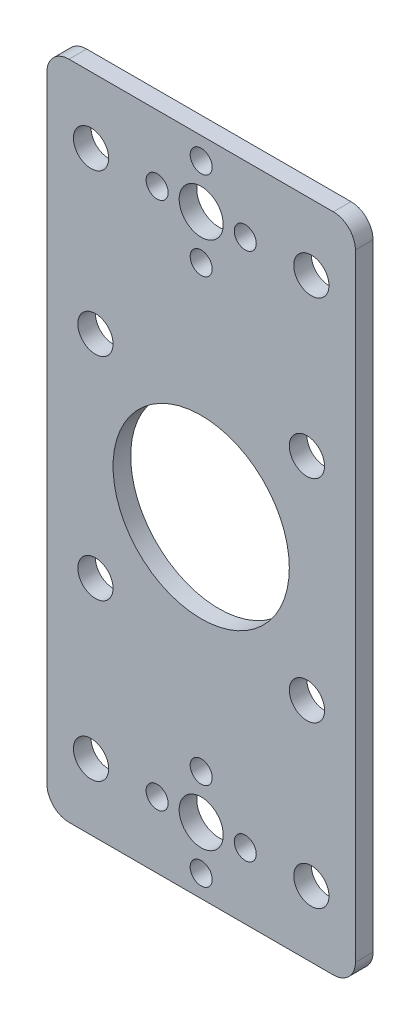
SolidWorks part; units mm, degrees
ref_plane "Front Plane" through (0, 0, 0) normal (0, 0, 1) x (1, 0, 0)
ref_plane "Top Plane" through (0, 0, 0) normal (0, 1, 0) x (1, 0, 0)
ref_plane "Right Plane" through (0, 0, 0) normal (1, 0, 0) x (0, 0, -1)
sketch "Sketch1" plane through (0, 0, 0) normal (0, 0, 1) x (1, 0, 0)
  line L0 (1.0283, 75.669) -> (1.0283, -74.331) construction
  line L1 (-59.1034, 0.669) -> (56.16, 0.669) construction
  line L2 (-50.4717, 60.669) -> (47.5283, 60.669) construction
  line L3 (36.0283, -74.331) -> (-33.9717, -74.331)
  line L4 (36.0283, -74.331) -> (36.0283, 75.669)
  line L5 (36.0283, 75.669) -> (-33.9717, 75.669)
  line L6 (-33.9717, -74.331) -> (-33.9717, 75.669)
  line L7 (36.0283, -74.331) -> (-33.9717, 75.669) construction
  line L8 (36.0283, 75.669) -> (-33.9717, -74.331) construction
  line L9 (-22.9717, -23.331) -> (25.0283, -23.331) construction
  line L10 (-22.9717, -23.331) -> (-22.9717, 24.669) construction
  line L11 (-22.9717, 24.669) -> (25.0283, 24.669) construction
  line L12 (25.0283, -23.331) -> (25.0283, 24.669) construction
  line L13 (-22.9717, -23.331) -> (25.0283, 24.669) construction
  line L14 (-22.9717, 24.669) -> (25.0283, -23.331) construction
  line L15 (-50.4717, -59.331) -> (47.5283, -59.331) construction
  circle A0 centre (1.0283, 0.669) radius 20
  circle A1 centre (-22.9717, 24.669) radius 4
  circle A2 centre (25.0283, 24.669) radius 4
  circle A3 centre (25.0283, -23.331) radius 4
  circle A4 centre (-22.9717, -23.331) radius 4
  circle A5 centre (26.0283, 60.669) radius 4
  circle A6 centre (-23.9717, 60.669) radius 4
  circle A7 centre (26.0283, -59.331) radius 4
  circle A8 centre (-23.9717, -59.331) radius 4
  point P4 (1.0283, 0.669)
  dimension "D3" = 8
  dimension "D4" = 8
  dimension "D1" = 70
  dimension "D2" = 48
  dimension "D5" = 10
  dimension "D6" = 10
  dimension "D7" = 10
  dimension "D8" = 10
  dimension "D9" = 75
base flange "Base-Flange1" sketch "Sketch1" thickness 4 reverse thickness direction no parameters "D1"=0.7366
fillet "Fillet1" radius 5 4 edges at (-33.9717, -74.331, -2) (36.0283, -74.331, -2) (36.0283, 75.669, -2) (-33.9717, 75.669, -2)
sketch "Sketch2" plane through (0, 0, 0) normal (0, 0, 1) x (1, 0, 0)
  line L0 (22.0283, 60.669) -> (-19.9717, 60.669) construction
  line L1 (77.0283, 0.669) -> (-46.9717, 0.669) construction
  line L2 (22.0283, -59.331) -> (-19.9717, -59.331) construction
  line L3 (22.0283, 60.669) -> (-19.9717, 60.669) construction
  line L4 (22.0283, -59.331) -> (-19.9717, -59.331) construction
  line L8 (-33.9717, 70.669) -> (-33.9717, -69.331) construction
  circle A0 centre (1.0283, 60.669) radius 5
  circle A1 centre (1.0283, -59.331) radius 5
  circle A2 centre (26.0283, 60.669) radius 4 construction
  circle A3 centre (-23.9717, 60.669) radius 4 construction
  circle A4 centre (26.0283, -59.331) radius 4 construction
  circle A5 centre (-23.9717, -59.331) radius 4 construction
  dimension "D1" = 10
  dimension "D2" = 60
  dimension "D3" = 35
extrude "Cut-Extrude1" cut sketch "Sketch2" against normal up to surface (4 mm away) and the other way through all normal cut yes up to face at (-19.9717, -59.331, -4)
sketch "Sketch3" plane through (0, 0, 0) normal (0, 0, 1) x (1, 0, 0)
  line L4 (36.0283, 0.669) -> (-33.9717, 0.669) construction
  line L5 (36.0283, -69.331) -> (36.0283, 70.669) construction
  line L6 (-33.9717, 70.669) -> (-33.9717, -69.331) construction
  circle A1 centre (1.0283, 60.669) radius 10 construction
  circle A2 centre (1.0283, 70.669) radius 2.5
  circle A3 centre (11.0283, 60.669) radius 2.5
  circle A4 centre (1.0283, 50.669) radius 2.5
  circle A5 centre (-8.9717, 60.669) radius 2.5
  circle A7 centre (1.0283, -59.331) radius 10 construction
  circle A9 centre (-8.9717, -59.331) radius 2.5
  circle A10 centre (1.0283, -49.331) radius 2.5
  circle A11 centre (11.0283, -59.331) radius 2.5
  circle A12 centre (1.0283, -69.331) radius 2.5
  circle A14 centre (1.0283, 60.669) radius 2.2657 construction
  dimension "D3" = 20
  dimension "D4" = 5
  dimension "D5" = 10
extrude "Cut-Extrude2" cut sketch "Sketch3" against normal up to surface (4 mm away) normal cut yes up to face at (6.0283, 60.669, -4)
sketch "Bend-Lines1" [suppressed] plane through (0, 0, 0) normal (0, 1, 0) x (1, 0, 0)
sketch "Bounding-Box1" [suppressed] plane through (0, 0, 0) normal (0, 1, 0) x (1, 0, 0)
sheet metal parameters "Sheet-Metal1" thickness 4 parameters "D1"=0.7366
flat pattern "Flat-Pattern1" [suppressed]
sketch "Bend-Lines2" plane through (0, 0, 0) normal (0, 1, 0) x (1, 0, 0)
sketch3d "Bounding-Box2" [suppressed]
  line L0 (36.0282, -74.331, 0) -> (36.0283, 75.669, 0) construction
  line L1 (-33.9717, -74.331, 0) -> (-33.9717, 75.669, 0) construction
  line L2 (36.0282, -74.331, 0) -> (-33.9717, -74.331, 0) construction
  line L3 (36.0283, 75.669, 0) -> (-33.9717, 75.669, 0) construction
sheet metal parameters "Sheet-Metal2" thickness 4 parameters "D1"=0.7366
flat pattern "Flat-Pattern1"
sketch "Bend-Lines2" plane through (0, 0, 0) normal (0, 1, 0) x (1, 0, 0)
sketch3d "Bounding-Box2" [suppressed]
  line L0 (36.0282, -74.331, 0) -> (36.0283, 75.669, 0) construction
  line L1 (-33.9717, -74.331, 0) -> (-33.9717, 75.669, 0) construction
  line L2 (36.0282, -74.331, 0) -> (-33.9717, -74.331, 0) construction
  line L3 (36.0283, 75.669, 0) -> (-33.9717, 75.669, 0) construction
sheet metal parameters "Sheet-Metal4" thickness 4 parameters "D1"=0.7366
flat pattern "Flat-Pattern1"
sketch "Bend-Lines2" plane through (0, 0, 0) normal (0, 1, 0) x (1, 0, 0)
sketch3d "Bounding-Box2" [suppressed]
  line L0 (36.0282, -74.331, 0) -> (36.0283, 75.669, 0) construction
  line L1 (-33.9717, -74.331, 0) -> (-33.9717, 75.669, 0) construction
  line L2 (36.0282, -74.331, 0) -> (-33.9717, -74.331, 0) construction
  line L3 (36.0283, 75.669, 0) -> (-33.9717, 75.669, 0) construction
